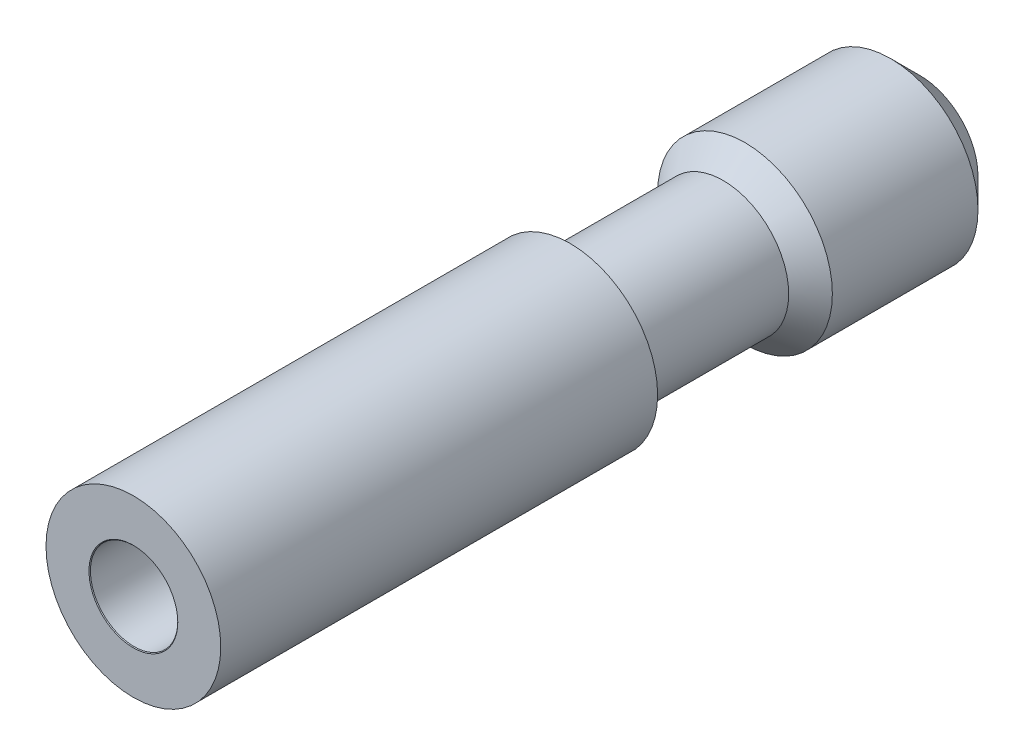
SolidWorks part; units mm, degrees
ref_plane "Plan de face" through (0, 0, 0) normal (0, 0, 1) x (1, 0, 0)
ref_plane "Plan de dessus" through (0, 0, 0) normal (0, 1, 0) x (1, 0, 0)
ref_plane "Plan de droite" through (0, 0, 0) normal (1, 0, 0) x (0, 0, -1)
sketch "Esquisse1" plane through (0, 0, 0) normal (0, 0, 1) x (1, 0, 0)
  circle A0 centre (0, 0) radius 3
extrude "Boss.-Extru.1" add sketch "Esquisse1" along normal blind 27
cosmetic thread "Représentation de filetage1" parameters "D1"=5, "D2"=4.891
hole_wizard "Diamètre du perçage Ø3.0 (3)1" positions "Esquisse3" profile "Esquisse4" hole size "Ø3.0" standard "ISO"
sketch "Esquisse3" plane through (0, 0, 27) normal (0, 0, 1) x (1, 0, 0)
  point P0 (0, 0)
sketch "Esquisse4" plane through (0, 0, 27) normal (1, 0, 0) x (0, -1, 0)
  line L0 (0, 0) -> (0, 25.4013)
  line L1 (0, 25.4013) -> (1.5, 24.5)
  line L2 (1.5, 24.5) -> (1.5, 0.025)
  line L3 (1.5, 0.025) -> (1.525, 0)
  line L5 (1.525, 0) -> (0, 0)
  line L6 (-1.5, 0.025) -> (-1.525, 0) construction
  line L10 (0, 25.4013) -> (-1.5, 24.5) construction
  line L11 (0, -6.35) -> (0, 107.95) construction
  dimension "Diamètre du perçage" = 3
  dimension "Profondeur du perçage" = 24.5
  dimension "Diamètre du fraisage entrant" = 3.05
  dimension "Angle du fraisage entrant" = 90
  dimension "Angle de pointe" = 118
hole_wizard "Diamètre du perçage Ø2.5 (2.5)1" positions "Esquisse6" profile "Esquisse7" hole size "Ø2.5" standard "ISO"
sketch "Esquisse6" plane through (0, 0, 0) normal (0, 0, -1) x (-1, 0, 0)
  point P0 (0, 0)
sketch "Esquisse7" plane through (0, 0, 0) normal (1, 0, 0) x (0, 1, 0)
  line L0 (0, 0) -> (0, 3.2511)
  line L1 (0, 3.2511) -> (1.25, 2.5)
  line L2 (1.25, 2.5) -> (1.25, 0)
  line L5 (1.25, 0) -> (0, 0)
  line L10 (0, 3.2511) -> (-1.25, 2.5) construction
  line L11 (0, -6.35) -> (0, 107.95) construction
  dimension "Diamètre du perçage" = 2.5
  dimension "Profondeur du perçage" = 2.5
  dimension "Angle de pointe" = 118
sketch "Esquisse8" plane through (0, 0, 27) normal (0, 0, 1) x (1, 0, 0)
  line L1 (-5.6929, 3.5093) -> (4.678, 3.5093)
  line L2 (-5.6929, 3.5093) -> (-5.6929, -3.6112)
  line L3 (-5.6929, -3.6112) -> (4.678, -3.6112)
  line L4 (4.678, 3.5093) -> (4.678, -3.6112)
  circle A0 centre (0, 0) radius 2.25
extrude "Enlèv. mat.-Extru.1" cut sketch "Esquisse8" against normal blind 6 from offset 15 offset against normal yes
chamfer "Chanfrein1" distance 1 angle 45 1 edges at (3, 0, 0)
chamfer "Chanfrein2" distance 0.75 angle 45 1 edges at (2.25, 0, 6)
